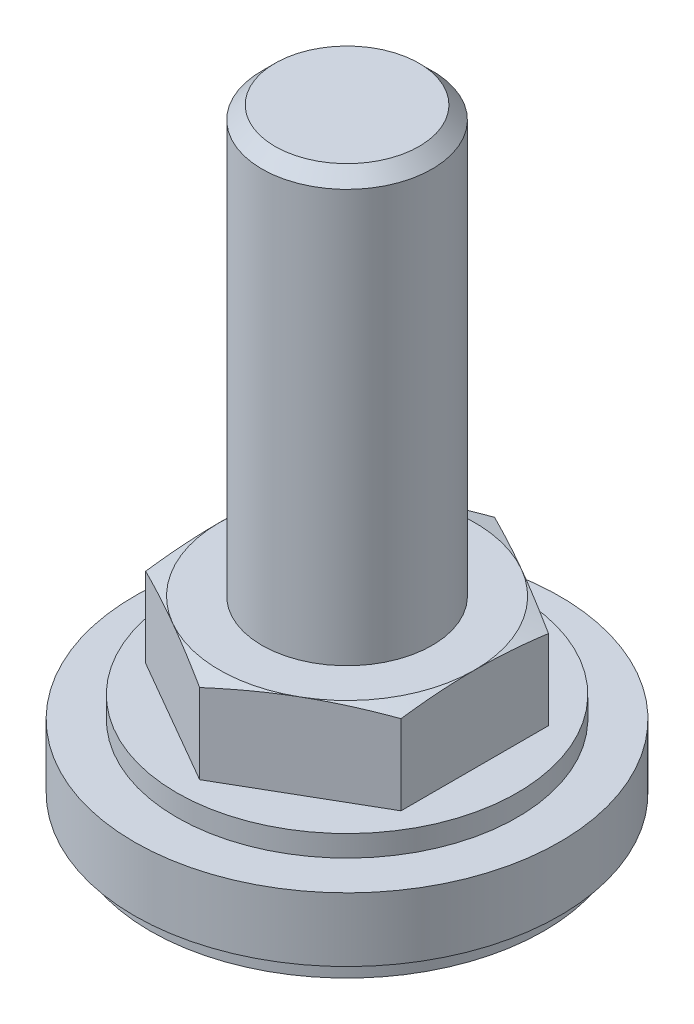
SolidWorks part; units mm, degrees
material "A6061"
ref_plane "前视基准面" through (0, 0, 0) normal (0, 0, 1) x (1, 0, 0)
ref_plane "上视基准面" through (0, 0, 0) normal (0, 1, 0) x (1, 0, 0)
ref_plane "右视基准面" through (0, 0, 0) normal (1, 0, 0) x (0, 0, -1)
sketch "草图1" plane through (0, 0, 0) normal (0, 0, 1) x (1, 0, 0)
  line L0 (0, 50) -> (6.773, 50)
  line L1 (6.773, 50) -> (8, 48.773)
  line L2 (8, 48.773) -> (8, 10)
  line L3 (8, 10) -> (12, 10)
  line L4 (12, 10) -> (15, 9.1962)
  line L5 (15, 9.1962) -> (15, 2)
  line L6 (15, 2) -> (16, 2)
  line L7 (16, 2) -> (16, 0)
  line L8 (16, 0) -> (20, 0)
  line L9 (20, 0) -> (20, -6)
  line L10 (20, -6) -> (18.5, -6)
  line L11 (18.5, -6) -> (18.5, -8)
  line L12 (18.5, -8) -> (0, -8)
  line L13 (0, -8) -> (0, 50)
  line L14 (0, -8) -> (0, 50) construction
revolve "旋转1" add sketch "草图1" angle 360 about L14 reverse direction yes
cosmetic thread "装饰螺纹线1" parameters "D1"=40, "D2"=13.546
ref_plane "基准面1" through (0, 2, 0) normal (0, 1, 0) x (1, 0, 0)
ref_plane "基准面2" through (0, 66, 0) normal (0, 1, 0) x (1, 0, 0)
sketch "草图2" plane through (0, 2, 0) normal (0, 1, 0) x (1, 0, 0)
  line L0 (-12, -6.9282) -> (0, -13.8564)
  line L1 (0, -13.8564) -> (12, -6.9282)
  line L2 (12, -6.9282) -> (12, 6.9282)
  line L3 (12, 6.9282) -> (0, 13.8564)
  line L4 (0, 13.8564) -> (-12, 6.9282)
  line L5 (-12, 6.9282) -> (-12, -6.9282)
  circle A0 centre (0, 0) radius 17
extrude "切除-拉伸1" cut sketch "草图2" along normal blind 10
ref_plane "基准面3" through (0, -8, 0) normal (0, 1, 0) x (1, 0, 0)
ref_plane "基准面4" through (0, 58, 0) normal (0, 1, 0) x (1, 0, 0)
ref_plane "adjuster_to_dummy XY" through (0, 58, 0) normal (0, 1, 0) x (1, 0, 0)
ref_plane "adjuster_to_dummy XZ" through (0, 0, 0) normal (0, 0, 1) x (1, 0, 0)
ref_plane "adjuster_to_dummy YZ" through (0, 0, 0) normal (1, 0, 0) x (0, 0, -1)
ref_axis "adjuster_to_dummy X" through (-80.9, 58, 0) along (1, 0, 0)
ref_axis "adjuster_to_dummy Y" through (0, 58, 50) along (0, 0, -1)
ref_axis "adjuster_to_dummy Z" through (0, 50, 0) along (0, -1, 0)
sketch3d "adjuster_to_dummy"
  point P0 (0, 58, 0)
